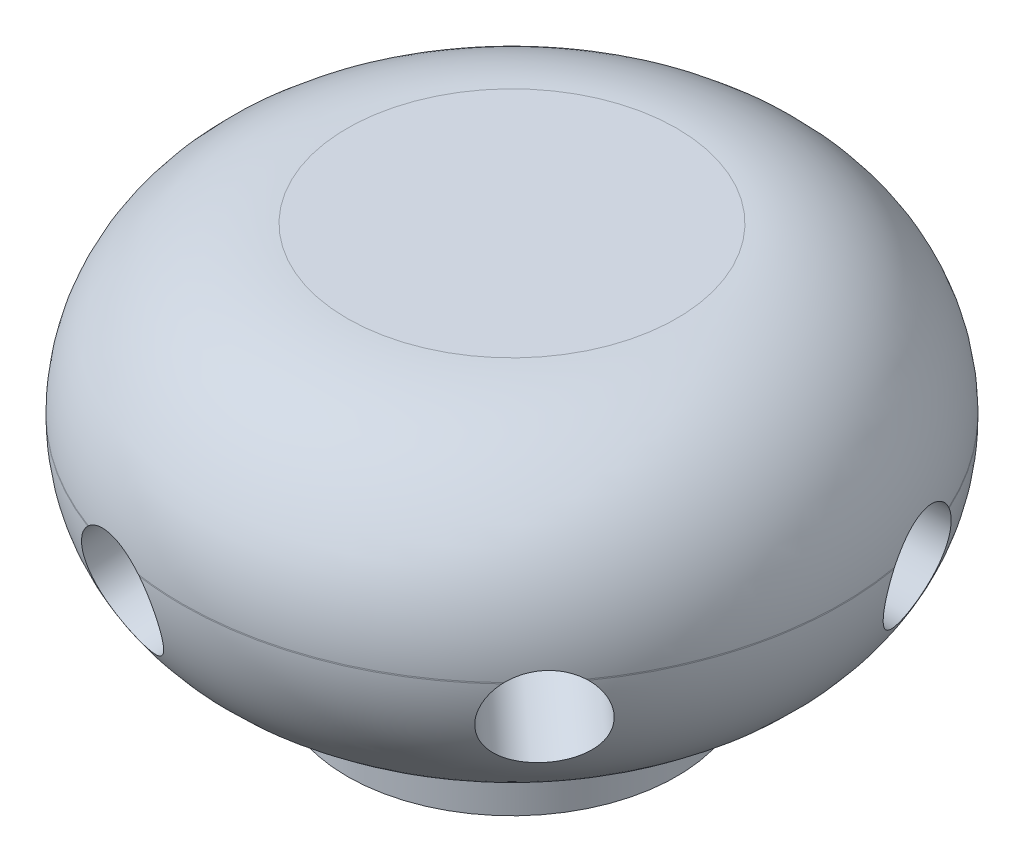
SolidWorks part; units mm, degrees
ref_plane "Front Plane" through (0, 0, 0) normal (0, 0, 1) x (1, 0, 0)
ref_plane "Top Plane" through (0, 0, 0) normal (0, 1, 0) x (1, 0, 0)
ref_plane "Right Plane" through (0, 0, 0) normal (1, 0, 0) x (0, 0, -1)
sketch "Sketch1" plane through (0, 0, 0) normal (0, 1, 0) x (1, 0, 0)
  circle A0 centre (0, 0) radius 10
  dimension "D1" = 20
extrude "base" add sketch "Sketch1" along normal blind 3.0354 and the other way blind 7
ref_axis "6hubaxis" through (0, 5.5, 0) along (0, -1, 0)
ref_plane "Plane1" through (2.6705, -1.0931, 2.7701) normal (-0.6676, 0.2733, -0.6925) x (-0.6559, 0.2243, 0.7208)
sketch "Sketch2" [suppressed] plane through (2.6705, -1.0931, 2.7701) normal (-0.6676, 0.2733, -0.6925) x (-0.6559, 0.2243, 0.7208)
  circle A0 centre (0, 0) radius 1.5 construction
  circle A1 centre (0, 0) radius 1.5
extrude "hole1" [suppressed] cut sketch "Sketch2" against normal through all
pattern_circular "hole1mirror" [suppressed] count 2 over 360 about axis through (0, 5.5, 0) along (0, -1, 0) of bodies 112
ref_plane "Plane2" through (-0.9417, -1.2361, 3.6858) normal (0.2354, 0.309, -0.9215) x (-0.9719, 0.0738, -0.2235)
sketch "Sketch3" plane through (-0.9417, -1.2361, 3.6858) normal (0.2354, 0.309, -0.9215) x (-0.9719, 0.0738, -0.2235)
  circle A0 centre (0, 0) radius 1.5 construction
  circle A1 centre (0, 0) radius 1.5 construction
  circle A2 centre (0, 0) radius 1.6
  dimension "D1" = 3.2
extrude "hole2" cut sketch "Sketch3" against normal through all
pattern_circular "hole2mirror" count 2 over 360 about axis through (0, 5.5, 0) along (0, -1, 0) of "hole2"
ref_plane "Plane3" through (-3.7178, -1.2361, 0.8061) normal (0.9295, 0.309, -0.2015) x (-0.1912, -0.0636, -0.9795)
sketch "Sketch4" plane through (-3.7178, -1.2361, 0.8061) normal (0.9295, 0.309, -0.2015) x (-0.1912, -0.0636, -0.9795)
  circle A0 centre (0, 0) radius 1.5 construction
  circle A1 centre (0, 0) radius 1.5 construction
  circle A2 centre (0, 0) radius 1.6
  dimension "D1" = 3.2
extrude "hole3" cut sketch "Sketch4" against normal through all
pattern_circular "hole3mirror" [suppressed] count 2 over 360 about axis through (0, 5.5, 0) along (0, -1, 0) of bodies 117
ref_plane "Plane4" through (3.672, -1.0931, -1.1497) normal (-0.918, 0.2733, 0.2874) x (0.2755, -0.082, 0.9578)
sketch "Sketch5" plane through (3.672, -1.0931, -1.1497) normal (-0.918, 0.2733, 0.2874) x (0.2755, -0.082, 0.9578)
  circle A0 centre (0, 0) radius 1.5 construction
  circle A1 centre (0, 0) radius 1.5
extrude "Cut-Extrude1" cut sketch "Sketch5" against normal through all
ref_plane "Plane5" through (2.8756, -1.2361, 2.4906) normal (-0.7189, 0.309, -0.6227) x (-0.572, 0.2459, 0.7825)
sketch "Sketch6" plane through (2.8756, -1.2361, 2.4906) normal (-0.7189, 0.309, -0.6227) x (-0.572, 0.2459, 0.7825)
  circle A0 centre (0, 0) radius 1.5 construction
  circle A1 centre (0, 0) radius 1.5
extrude "Cut-Extrude2" cut sketch "Sketch6" against normal through all
ref_plane "Plane6" through (-2.6705, -1.0931, -2.7701) normal (0.6676, 0.2733, 0.6925) x (0.7445, -0.2451, -0.621)
sketch "Sketch7" plane through (-2.6705, -1.0931, -2.7701) normal (0.6676, 0.2733, 0.6925) x (0.7445, -0.2451, -0.621)
  circle A0 centre (0, 0) radius 1.5 construction
  circle A1 centre (0, 0) radius 1.5
extrude "Cut-Extrude3" cut sketch "Sketch7" against normal through all
fillet "Fillet1" radius 5 2 edges at (0, -7, 10) (0, 3.0354, 10)
sketch "Sketch8" plane through (0, -7, 0) normal (0, -1, 0) x (1, 0, 0)
  circle A0 centre (0, 0) radius 5
extrude "Boss-Extrude1" add sketch "Sketch8" along normal blind 2
